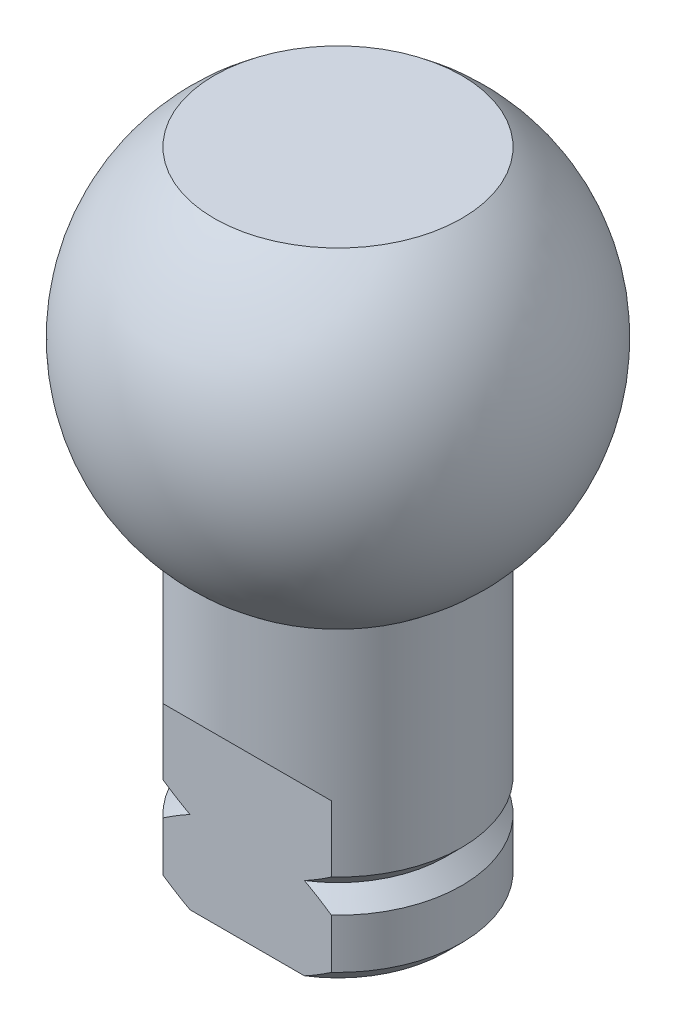
SolidWorks part; units mm, degrees
ref_plane "Front Plane" through (0, 0, 0) normal (0, 0, 1) x (1, 0, 0)
ref_plane "Top Plane" through (0, 0, 0) normal (0, 1, 0) x (1, 0, 0)
ref_plane "Right Plane" through (0, 0, 0) normal (1, 0, 0) x (0, 0, -1)
sketch "Sketch1" plane through (0, 0, 0) normal (0, 1, 0) x (1, 0, 0)
  circle A0 centre (0, 0) radius 7.5
extrude "Boss-Extrude1" add sketch "Sketch1" along normal blind 20
sketch "Sketch2" plane through (0, 0, 0) normal (0, 0, 1) x (1, 0, 0)
  line L0 (7.5, 19) -> (7.5, 20)
  line L1 (7.5, 20) -> (-7.5, 20) construction
  line L2 (7.5, 20) -> (0, 20)
  line L3 (0, 41.5) -> (0, 39) construction
  line L4 (0, 39) -> (7.5, 39)
  line L6 (0, 29) -> (0, 20) construction
  line L7 (0, 20) -> (0, 39)
  line L8 (0, 29) -> (12.5, 29) construction
  arc A2 (7.5, 39) -> (7.5, 19) centre (0, 29) cw
revolve "Revolve1" add sketch "Sketch2" angle 360 about L7
sketch "Sketch3" plane through (0, 0, 0) normal (0, -1, 0) x (-1, 0, 0)
  line L0 (0, -7.5) -> (0, -5.5) construction
  line L2 (-5.099, -5.5) -> (0, -5.5)
  line L3 (0, -5.5) -> (5.099, -5.5)
  circle A1 centre (0, 0) radius 7.5 construction
  circle A2 centre (0, 0) radius 7.5 construction
  arc A4 (-5.099, -5.5) -> (5.099, -5.5) centre (0, 0) ccw
extrude "Cut-Extrude2" cut sketch "Sketch3" against normal blind 12 contours A4 L3 L2
ref_plane "SnapFeaturePlane" through (0, 5, 0) normal (0, 1, 0) x (1, 0, 0)
sketch "Sketch4" plane through (0, 5, 0) normal (0, 1, 0) x (1, 0, 0)
  line L0 (0, -5.5) -> (0, -4.4476) construction
  line L1 (5.099, -5.5) -> (-5.099, -5.5) construction
  line L8 (0, 7.5) -> (0, 6.5) construction
  line L9 (0, 7.5) -> (0, 8.5) construction
  line L10 (-1.381, -6.3516) -> (-1.8059, -8.3059)
  line L12 (1.8059, -8.3059) -> (1.381, -6.3516)
  arc A6 (5.099, -5.5) -> (-5.099, -5.5) centre (0, 0) ccw construction
  arc A9 (0, 6.5) -> (-1.381, -6.3516) centre (0, 0) ccw
  arc A10 (0, 6.5) -> (1.381, -6.3516) centre (0, 0) cw
  arc A11 (0, 8.5) -> (-1.8059, -8.3059) centre (0, 0) ccw
  arc A12 (0, 8.5) -> (1.8059, -8.3059) centre (0, 0) cw
extrude "Cut-Extrude4" cut sketch "Sketch4" against normal mid plane 2 contours A12 L12 A10 A9 L10 A11
chamfer "Chamfer1" distance 1 angle 45 2 edges at (0, 6, -6.5) (0, 4, -6.5)
chamfer "Chamfer3" distance 2 angle 45 1 edges at (0, 12, 5.5)
chamfer "Chamfer4" distance 1 angle 45 1 edges at (0, 0, -7.5)
